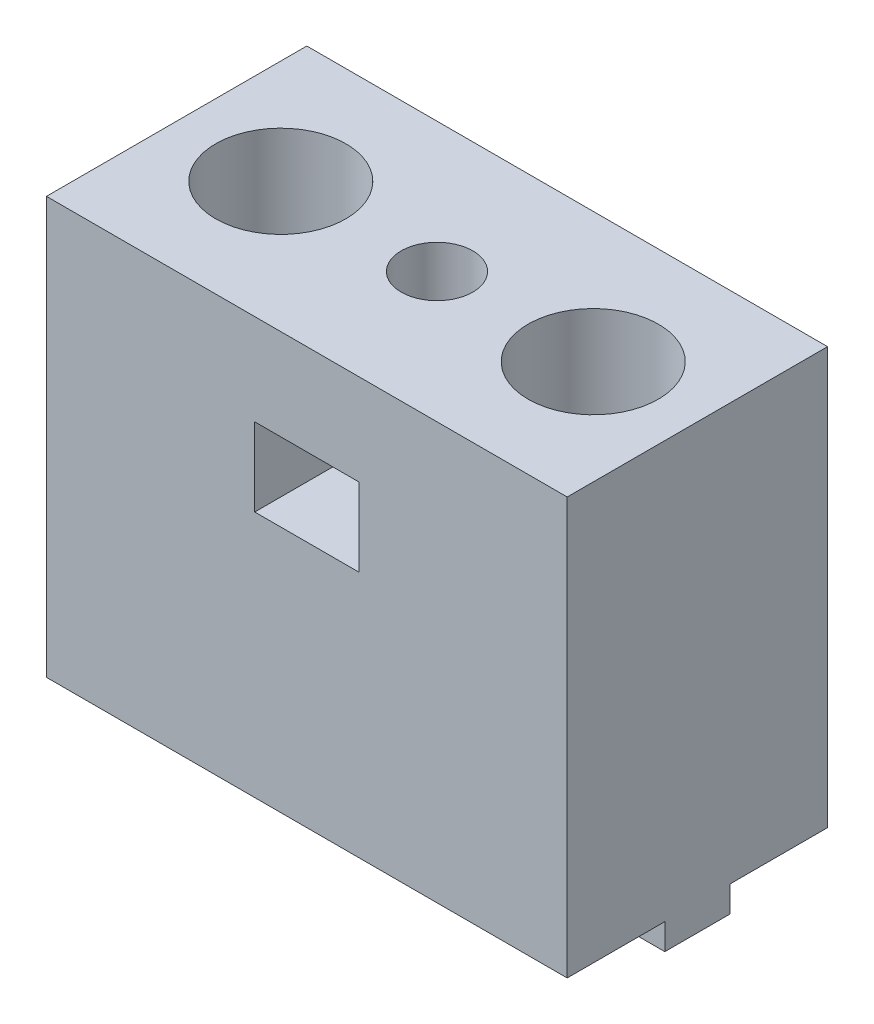
SolidWorks part; units mm, degrees
ref_plane "Front Plane" through (0, 0, 0) normal (0, 0, 1) x (1, 0, 0)
ref_plane "Top Plane" through (0, 0, 0) normal (0, 1, 0) x (1, 0, 0)
ref_plane "Right Plane" through (0, 0, 0) normal (1, 0, 0) x (0, 0, -1)
sketch "Sketch1" plane through (0, 0, 0) normal (0, 1, 0) x (1, 0, 0)
  line L1 (0, 0) -> (40, 0)
  line L2 (0, 0) -> (0, 20)
  line L3 (0, 20) -> (40, 20)
  line L4 (40, 0) -> (40, 20)
  dimension "D1" = 20
  dimension "D2" = 40
extrude "Boss-Extrude1" add sketch "Sketch1" along normal blind 32
sketch "Sketch2" plane through (0, 0, 0) normal (0, -1, 0) x (1, 0, 0)
  line L0 (40, 0) -> (40, -20) construction
  line L1 (40, -7.5) -> (0, -7.5)
  line L2 (40, -7.5) -> (40, -12.5)
  line L3 (40, -12.5) -> (0, -12.5)
  line L4 (0, -7.5) -> (0, -12.5)
  line L5 (0, -20) -> (0, 0) construction
  line L6 (40, -20) -> (0, -20) construction
  line L7 (0, 0) -> (40, 0) construction
  dimension "D1" = 7.5
  dimension "D2" = 7.5
extrude "Boss-Extrude2" add sketch "Sketch2" along normal blind 2
sketch "Sketch3" plane through (0, 32, 0) normal (0, 1, 0) x (1, 0, 0)
  line L0 (0, 20) -> (0, 0) construction
  line L1 (40, 0) -> (40, 20) construction
  line L2 (40, 20) -> (0, 20) construction
  circle A0 centre (20, 10) radius 2.75
  circle A1 centre (32, 10) radius 2.75
  circle A2 centre (8, 10) radius 2.75
  point P6 (0, 0)
  dimension "D1" = 5.5
  dimension "D2" = 5.5
  dimension "D3" = 5.5
  dimension "D4" = 8
  dimension "D5" = 8
  dimension "D6" = 20
  dimension "D7" = 10
  dimension "D8" = 10
  dimension "D9" = 10
extrude "Cut-Extrude1" cut sketch "Sketch3" against normal through all
sketch "Sketch4" plane through (0, 32, 0) normal (0, 1, 0) x (1, 0, 0)
  circle A0 centre (8, 10) radius 5
  circle A1 centre (32, 10) radius 5
  dimension "D1" = 10
  dimension "D2" = 10
extrude "Cut-Extrude2" cut sketch "Sketch4" against normal offset from surface (27 mm away) 5 up to face at (20, 0, -14.075)
sketch "Sketch5" plane through (0, 0, 0) normal (0, 0, 1) x (1, 0, 0)
  line L0 (0, 32) -> (0, 0) construction
  line L1 (16, 19) -> (24, 19)
  line L2 (16, 19) -> (16, 25)
  line L3 (16, 25) -> (24, 25)
  line L4 (24, 19) -> (24, 25)
  line L5 (0, 32) -> (40, 32) construction
  dimension "D1" = 6
  dimension "D2" = 8
  dimension "D3" = 16
  dimension "D4" = 7
extrude "Cut-Extrude3" cut sketch "Sketch5" against normal through all
